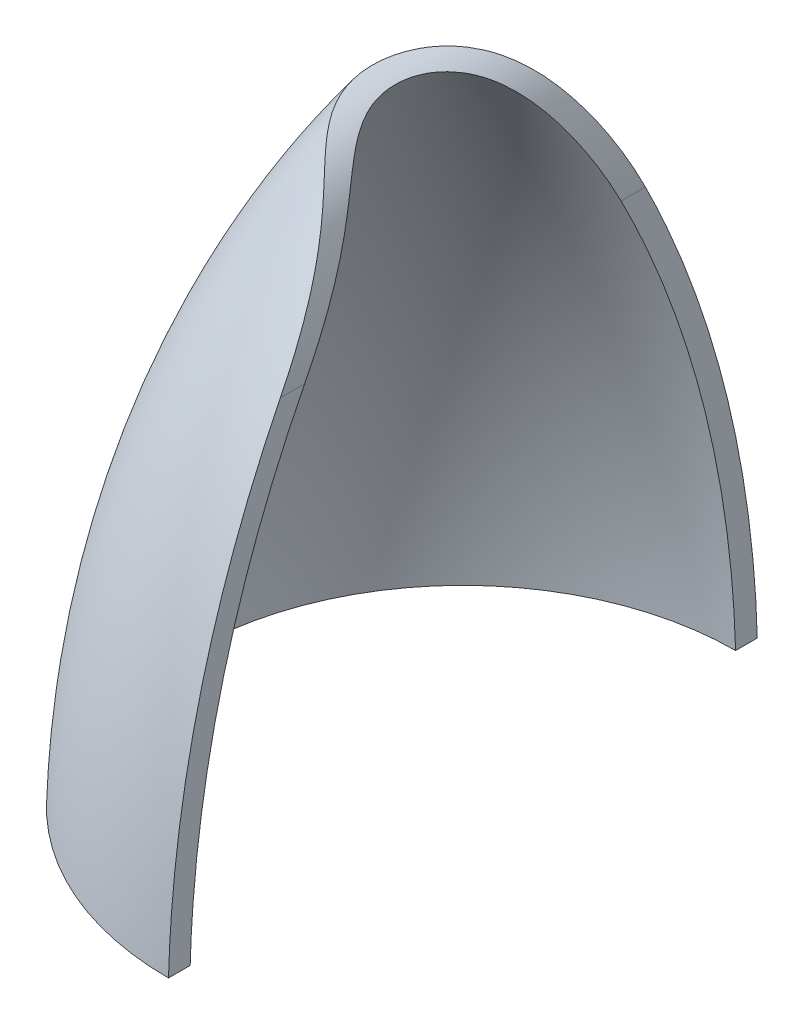
SolidWorks part; units mm, degrees
ref_plane "Front Plane" through (0, 0, 0) normal (0, 0, 1) x (1, 0, 0)
ref_plane "Top Plane" through (0, 0, 0) normal (0, 1, 0) x (1, 0, 0)
ref_plane "Right Plane" through (0, 0, 0) normal (1, 0, 0) x (0, 0, -1)
sketch "Sketch2" plane through (0, 0, 0) normal (0, 0, 1) x (1, 0, 0)
  line L0 (0, 0) -> (0, 170)
  line L1 (0, 0) -> (68, 0)
  arc A1 (0, 170) -> (68, 0) centre (-178.5, 0) cw
  dimension "D3" = 246.5
  dimension "D1" = 170
  dimension "D2" = 68
revolve "Revolve1" add sketch "Sketch2" angle 360 about L0
shell "Shell1" thickness 5 removed face at (0, 0, -68)
sketch "Sketch3" plane through (0, 0, 0) normal (0, 0, 1) x (1, 0, 0)
  line L0 (-68, 0) -> (68, 0) construction
  line L1 (0.016, 110) -> (0.016, 7)
  line L2 (0.016, 7) -> (-67.9006, 7)
  arc A1 (0, 170) -> (-68, 0) centre (178.5, 0) ccw construction
  spline S0 degree 3 poles (-20.842, 145) (-3.5273, 142.6868) (0.016, 125.1978) (0.016, 110) knots 0 0 0 0 1 1 1 1
  dimension "D4" = 45
  dimension "D7" = 30
  dimension "D1" = 60
  dimension "D2" = 25
  dimension "D3" = 32
  dimension "D5" = 7.5
  dimension "D6" = 7
split "Split4" trim tools "Sketch3" bodies to split 101 resulting bodies 106 107
delete or keep bodies "Body-Delete/Keep 1" type delete bodies bodies 107
